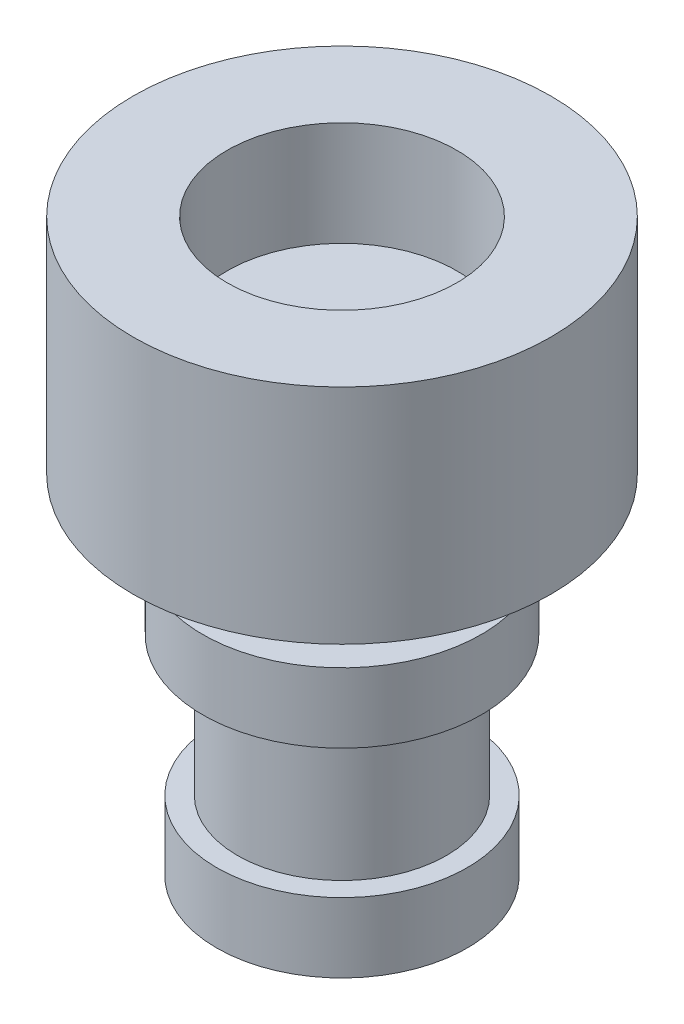
SolidWorks part; units mm, degrees
ref_plane "Front Plane" through (0, 0, 0) normal (0, 0, 1) x (1, 0, 0)
ref_plane "Top Plane" through (0, 0, 0) normal (0, 1, 0) x (1, 0, 0)
ref_plane "Right Plane" through (0, 0, 0) normal (1, 0, 0) x (0, 0, -1)
sketch "Sketch1" plane through (0, 0, 0) normal (0, 1, 0) x (1, 0, 0)
  circle A0 centre (-0.522, 0.5111) radius 1.6
  circle A1 centre (-0.522, 0.5111) radius 3
  dimension "D1" = 3.2
  dimension "D2" = 6
extrude "Boss-Extrude1" add sketch "Sketch1" along normal blind 3.2 contours A1
extrude "Boss-Extrude2" add sketch "Sketch1<3>" along normal blind 1 contours A0 region at (-0.522, 0, -0.5111)
sketch "Sketch1<3>" plane through (0, 0, 0) normal (0, 1, 0) x (1, 0, 0) same geometry as "Sketch1"
sketch "Sketch5" plane through (0, 0, 0) normal (0, -1, 0) x (1, 0, 0)
  circle A2 centre (-0.522, -0.5111) radius 1.5
  circle A3 centre (-0.522, -0.5111) radius 1.5
  dimension "D2" = 3
  dimension "D1" = 1.5
extrude "Boss-Extrude3" add sketch "Sketch5" along normal blind 1 contours A3
sketch "Sketch6" plane through (0, -1, 0) normal (0, -1, 0) x (1, 0, 0)
  circle A0 centre (-0.522, -0.5111) radius 2
  dimension "D1" = 4
extrude "Boss-Extrude4" add sketch "Sketch6" along normal blind 1
sketch "Sketch8" plane through (0, -2, 0) normal (0, -1, 0) x (-1, 0, 0)
  circle A0 centre (0.522, 0.5111) radius 1.5
  dimension "D1" = 3
extrude "Boss-Extrude5" add sketch "Sketch8" along normal blind 3 contours A0
sketch "Sketch10" plane through (0, -5, 0) normal (0, -1, 0) x (1, 0, 0)
  circle A0 centre (-0.522, -0.5111) radius 1.8
extrude "Boss-Extrude6" add sketch "Sketch10" against normal blind 1
sketch "Sketch11" plane through (0, 3.2, 0) normal (0, 1, 0) x (1, 0, 0)
  text T0 "VIII" font "Century Gothic" height in points 5
sketch "Sketch12" plane through (0, 3.2, 0) normal (0, 1, 0) x (1, 0, 0)
  circle A0 centre (-0.522, 0.5111) radius 1.65
extrude "Cut-Extrude1" cut sketch "Sketch12" against normal blind 1.5
